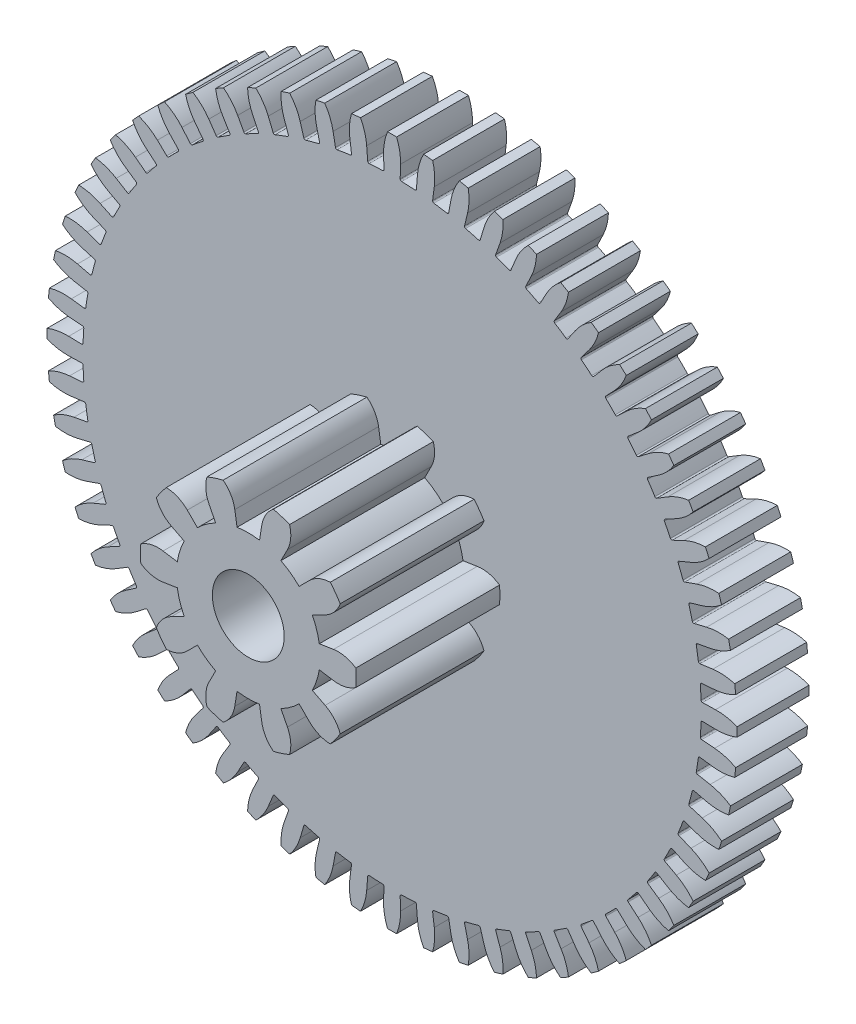
SolidWorks part; units mm, degrees
ref_plane "Front Plane" through (0, 0, 0) normal (0, 0, 1) x (1, 0, 0)
ref_plane "Top Plane" through (0, 0, 0) normal (0, 1, 0) x (1, 0, 0)
ref_plane "Right Plane" through (0, 0, 0) normal (1, 0, 0) x (0, 0, -1)
sketch "Sketch1" plane through (0, 0, 0) normal (0, 0, 1) x (1, 0, 0)
  line L0 (0, 0) -> (6.94, 0) construction
  line L1 (0, 0) -> (4.2941, 0.225) construction
  line L2 (0, 0) -> (5.3526, 0.1402) construction
  line L3 (0, 0) -> (5.9482, 0.0779) construction
  line L4 (4.2985, 0.1126) -> (4.4985, 0.1178)
  line L5 (0, 0) -> (4.2941, 0.225)
  line L6 (4.2985, -0.1126) -> (4.4985, -0.1178)
  line L7 (0, 0) -> (4.2941, -0.225) construction
  line L8 (0, 0) -> (4.2941, -0.225)
  arc A0 (4.8, 0) -> (4.7984, 0.1256) centre (0, 0) ccw construction
  circle A1 centre (0, 0) radius 4.5 construction
  arc A2 (4.2985, 0.1126) -> (4.3, 0) centre (0, 0) ccw construction
  arc A3 (4.4985, 0.1178) -> (4.7996, 0.0628) centre (4.518, -0.6276) cw
  arc A4 (4.7996, 0.0628) -> (4.7996, -0.0628) centre (0, 0) cw
  arc A5 (4.2941, 0.225) -> (4.2985, 0.1126) centre (0, 0) cw
  arc A6 (4.4985, -0.1178) -> (4.7996, -0.0628) centre (4.518, 0.6276) ccw
  arc A7 (4.2941, -0.225) -> (4.2985, -0.1126) centre (0, 0) ccw
  circle A8 centre (0, 0) radius 4.8 construction
  dimension "D1" = 9.6
  dimension "D2" = 9
  dimension "D3" = 0.5
  dimension "D7" = 4.3
  dimension "D4" = 3
  dimension "D5" = 1.5
  dimension "D6" = 0.75
extrude "Boss-Extrude1" add sketch "Sketch1" along normal blind 1 contours L8 A7 L6 A6 A4 A3 L4 A5 L5 region at (3.0311, 0, 0)
fillet "Fillet1" radius 0.02 2 edges at (4.2985, -0.1126, 0.5) (4.2985, 0.1126, 0.5)
pattern_circular "CirPattern1" count 60 over 360 about axis through (0, 0, 1) along (0, 0, -1) of "Fillet1", "Boss-Extrude1"
ref_plane "Plane1" through (4.2606, -0.581, 1) normal (0.1351, 0.9908, 0) x (0.9908, -0.1351, 0)
sketch "Sketch4" plane through (0, 0, 1) normal (0, 0, 1) x (1, 0, 0)
  circle A0 centre (0, 0) radius 0.5
sketch "Sketch5" plane through (0, 0, 1) normal (0, 0, 1) x (1, 0, 0)
  line L4 (0.9877, 0.1564) -> (1.1852, 0.1877)
  line L5 (0.9877, -0.1564) -> (1.1852, -0.1877)
  line L6 (0.891, -0.454) -> (1.0692, -0.5448)
  line L7 (0.7071, -0.7071) -> (0.8485, -0.8485)
  line L8 (0.454, -0.891) -> (0.5448, -1.0692)
  line L9 (0.1564, -0.9877) -> (0.1877, -1.1852)
  line L10 (-0.1564, -0.9877) -> (-0.1877, -1.1852)
  line L11 (-0.454, -0.891) -> (-0.5448, -1.0692)
  line L12 (-0.7071, -0.7071) -> (-0.8485, -0.8485)
  line L13 (-0.891, -0.454) -> (-1.0692, -0.5448)
  line L14 (-0.9877, -0.1564) -> (-1.1852, -0.1877)
  line L15 (-0.9877, 0.1564) -> (-1.1852, 0.1877)
  line L16 (-0.891, 0.454) -> (-1.0692, 0.5448)
  line L17 (-0.7071, 0.7071) -> (-0.8485, 0.8485)
  line L18 (-0.454, 0.891) -> (-0.5448, 1.0692)
  line L19 (-0.1564, 0.9877) -> (-0.1877, 1.1852)
  line L20 (0.1564, 0.9877) -> (0.1877, 1.1852)
  line L21 (0.454, 0.891) -> (0.5448, 1.0692)
  line L22 (0.7071, 0.7071) -> (0.8485, 0.8485)
  line L23 (0.891, 0.454) -> (1.0692, 0.5448)
  arc A3 (1.1852, 0.1877) -> (1.4954, 0.1177) centre (1.2524, -0.2365) cw
  arc A4 (1.4954, 0.1177) -> (1.4954, -0.1177) centre (0, 0) cw
  arc A5 (0.9511, 0.309) -> (0.9877, 0.1564) centre (0, 0) cw
  arc A6 (1.1852, -0.1877) -> (1.4954, -0.1177) centre (1.2524, 0.2365) ccw
  arc A7 (0.9511, -0.309) -> (0.9877, -0.1564) centre (0, 0) ccw
  arc A8 (0.9511, -0.309) -> (0.891, -0.454) centre (0, 0) cw
  arc A9 (1.0692, -0.5448) -> (1.279, -0.7837) centre (0.8742, -0.9275) cw
  arc A10 (1.279, -0.7837) -> (1.1406, -0.9742) centre (0, 0) cw
  arc A11 (0.8485, -0.8485) -> (1.1406, -0.9742) centre (1.1522, -0.5448) ccw
  arc A12 (0.5878, -0.809) -> (0.7071, -0.7071) centre (0, 0) ccw
  arc A13 (0.5878, -0.809) -> (0.454, -0.891) centre (0, 0) cw
  arc A14 (0.5448, -1.0692) -> (0.574, -1.3858) centre (0.1621, -1.2642) cw
  arc A15 (0.574, -1.3858) -> (0.3502, -1.4586) centre (0, 0) cw
  arc A16 (0.1877, -1.1852) -> (0.3502, -1.4586) centre (0.6119, -1.118) ccw
  arc A17 (0, -1) -> (0.1564, -0.9877) centre (0, 0) ccw
  arc A18 (0, -1) -> (-0.1564, -0.9877) centre (0, 0) cw
  arc A19 (-0.1877, -1.1852) -> (-0.3502, -1.4586) centre (-0.6119, -1.118) cw
  arc A20 (-0.3502, -1.4586) -> (-0.574, -1.3858) centre (0, 0) cw
  arc A21 (-0.5448, -1.0692) -> (-0.574, -1.3858) centre (-0.1621, -1.2642) ccw
  arc A22 (-0.5878, -0.809) -> (-0.454, -0.891) centre (0, 0) ccw
  arc A23 (-0.5878, -0.809) -> (-0.7071, -0.7071) centre (0, 0) cw
  arc A24 (-0.8485, -0.8485) -> (-1.1406, -0.9742) centre (-1.1522, -0.5448) cw
  arc A25 (-1.1406, -0.9742) -> (-1.279, -0.7837) centre (0, 0) cw
  arc A26 (-1.0692, -0.5448) -> (-1.279, -0.7837) centre (-0.8742, -0.9275) ccw
  arc A27 (-0.9511, -0.309) -> (-0.891, -0.454) centre (0, 0) ccw
  arc A28 (-0.9511, -0.309) -> (-0.9877, -0.1564) centre (0, 0) cw
  arc A29 (-1.1852, -0.1877) -> (-1.4954, -0.1177) centre (-1.2524, 0.2365) cw
  arc A30 (-1.4954, -0.1177) -> (-1.4954, 0.1177) centre (0, 0) cw
  arc A31 (-1.1852, 0.1877) -> (-1.4954, 0.1177) centre (-1.2524, -0.2365) ccw
  arc A32 (-0.9511, 0.309) -> (-0.9877, 0.1564) centre (0, 0) ccw
  arc A33 (-0.9511, 0.309) -> (-0.891, 0.454) centre (0, 0) cw
  arc A34 (-1.0692, 0.5448) -> (-1.279, 0.7837) centre (-0.8742, 0.9275) cw
  arc A35 (-1.279, 0.7837) -> (-1.1406, 0.9742) centre (0, 0) cw
  arc A36 (-0.8485, 0.8485) -> (-1.1406, 0.9742) centre (-1.1522, 0.5448) ccw
  arc A37 (-0.5878, 0.809) -> (-0.7071, 0.7071) centre (0, 0) ccw
  arc A38 (-0.5878, 0.809) -> (-0.454, 0.891) centre (0, 0) cw
  arc A39 (-0.5448, 1.0692) -> (-0.574, 1.3858) centre (-0.1621, 1.2642) cw
  arc A40 (-0.574, 1.3858) -> (-0.3502, 1.4586) centre (0, 0) cw
  arc A41 (-0.1877, 1.1852) -> (-0.3502, 1.4586) centre (-0.6119, 1.118) ccw
  arc A42 (0, 1) -> (-0.1564, 0.9877) centre (0, 0) ccw
  arc A43 (0, 1) -> (0.1564, 0.9877) centre (0, 0) cw
  arc A44 (0.1877, 1.1852) -> (0.3502, 1.4586) centre (0.6119, 1.118) cw
  arc A45 (0.3502, 1.4586) -> (0.574, 1.3858) centre (0, 0) cw
  arc A46 (0.5448, 1.0692) -> (0.574, 1.3858) centre (0.1621, 1.2642) ccw
  arc A47 (0.5878, 0.809) -> (0.454, 0.891) centre (0, 0) ccw
  arc A48 (0.5878, 0.809) -> (0.7071, 0.7071) centre (0, 0) cw
  arc A49 (0.8485, 0.8485) -> (1.1406, 0.9742) centre (1.1522, 0.5448) cw
  arc A50 (1.1406, 0.9742) -> (1.279, 0.7837) centre (0, 0) cw
  arc A51 (1.0692, 0.5448) -> (1.279, 0.7837) centre (0.8742, 0.9275) ccw
  arc A52 (0.9511, 0.309) -> (0.891, 0.454) centre (0, 0) ccw
  circle A53 centre (0, 0) radius 1.5 construction
  circle A54 centre (0, 0) radius 1 construction
  circle A55 centre (0, 0) radius 1.2 construction
  point P113 (0, 0)
  dimension "D1" = 3
  dimension "D2" = 2.4
  dimension "D3" = 1
  dimension "D4" = 0.5
  dimension "D7" = 10
extrude "Boss-Extrude2" add sketch "Sketch5" along normal blind 2
extrude "Cut-Extrude1" cut sketch "Sketch4" against normal blind 1 and the other way blind 2
